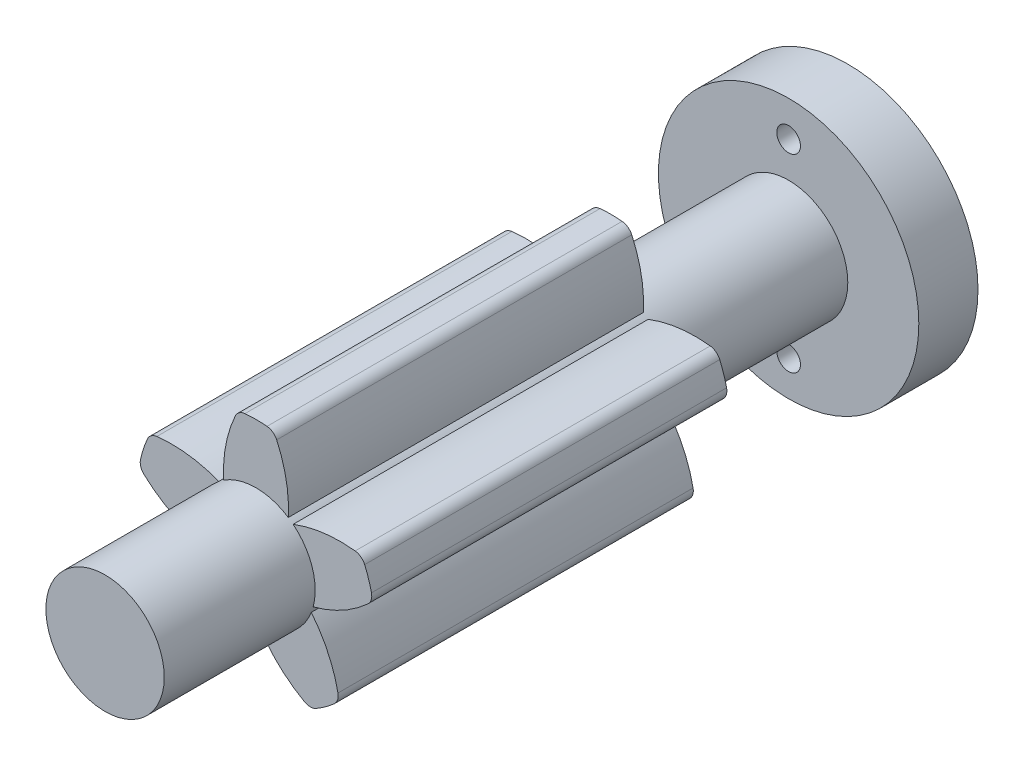
SolidWorks part; units mm, degrees
ref_plane "Plan de face" through (0, 0, 0) normal (0, 0, 1) x (1, 0, 0)
ref_plane "Plan de dessus" through (0, 0, 0) normal (0, 1, 0) x (1, 0, 0)
ref_plane "Plan de droite" through (0, 0, 0) normal (1, 0, 0) x (0, 0, -1)
sketch "Esquisse1" plane through (0, 0, 0) normal (0, 0, 1) x (1, 0, 0)
  circle A0 centre (0, 0) radius 11
  dimension "D1" = 22
extrude "Boss.-Extru.1" add sketch "Esquisse1" along normal blind 5
sketch "Esquisse2" plane through (0, 0, 5) normal (0, 0, 1) x (1, 0, 0)
  line L0 (0, 9.4533) -> (0, -10.2047) construction
  circle A0 centre (0, 0) radius 8
  circle A1 centre (0, 8) radius 1
  circle A2 centre (0, -8) radius 1
  dimension "D1" = 16
  dimension "D2" = 2
extrude "Enlèv. mat.-Extru.1" cut sketch "Esquisse2" against normal through all contours A1 L0 A0 | L0 A1 A0 | L0 A0 A1 | A0 L0 A1 | A2 L0 A0 | L0 A2 A0 | L0 A0 A2 | A0 L0 A2 region at (0.4328, 8.413, 5) region at (-0.4328, 8.413, 5) region at (0.4155, 7.5645, 5) region at (-0.4155, 7.5645, 5) region at (-0.4155, -7.5645, 5) region at (-0.4328, -8.413, 5) region at (0.4155, -7.5645, 5) region at (0.4328, -8.413, 5)
sketch "Esquisse3" plane through (0, 0, 5) normal (0, 0, 1) x (1, 0, 0)
  circle A0 centre (0, 0) radius 5
  dimension "D1" = 10
extrude "Boss.-Extru.2" add sketch "Esquisse3" along normal blind 57.75
ref_plane "Plan1" through (0, 0, 35) normal (0, 0, 1) x (1, 0, 0)
sketch "Esquisse4" plane through (0, 0, 35) normal (0, 0, 1) x (1, 0, 0)
  line L0 (0, 7) -> (0, 0) construction
  line L1 (-2.5, 7.1206) -> (2.5, 7.1206) construction
  line L2 (0, 0) -> (10, 0) construction
  circle A0 centre (0, 0) radius 5 construction
  circle A1 centre (0, 8) radius 1 construction
  circle A2 centre (0, 0) radius 10 construction
  circle A3 centre (0, 0) radius 5 construction
  arc A4 (-2.7312, 4.1882) -> (-1.5, 9.8869) centre (8.2519, 4.7977) cw
  arc A5 (1.5, 9.8869) -> (2.7312, 4.1882) centre (-8.2519, 4.7977) cw
  arc A6 (-1.5, 9.8869) -> (1.5, 9.8869) centre (0, 0) cw
  circle A8 centre (0, 0) radius 5
  arc A9 (-2.7312, 4.1882) -> (2.7312, 4.1882) centre (0, 0) ccw
  point P11 (0, 5)
  point P13 (5, 0)
  point P14 (10, 0)
  point P20 (-2.5, 7.1206)
  point P21 (2.5, 7.1206)
  dimension "D1" = 11
  dimension "D2" = 5
  dimension "D3" = 5
  dimension "D4" = 3
  dimension "D5" = 0
extrude "Boss.-Extru.3" add sketch "Esquisse4" along normal mid plane 30
fillet "Congé1" radius 1 2 edges at (1.5, 9.8869, 35) (-1.5, 9.8869, 35)
pattern_circular "Répétition circulaire1" count 5 every 72 about axis through (0, 0, 62.75) along (0, 0, -1) of "Boss.-Extru.3", "Congé1"
